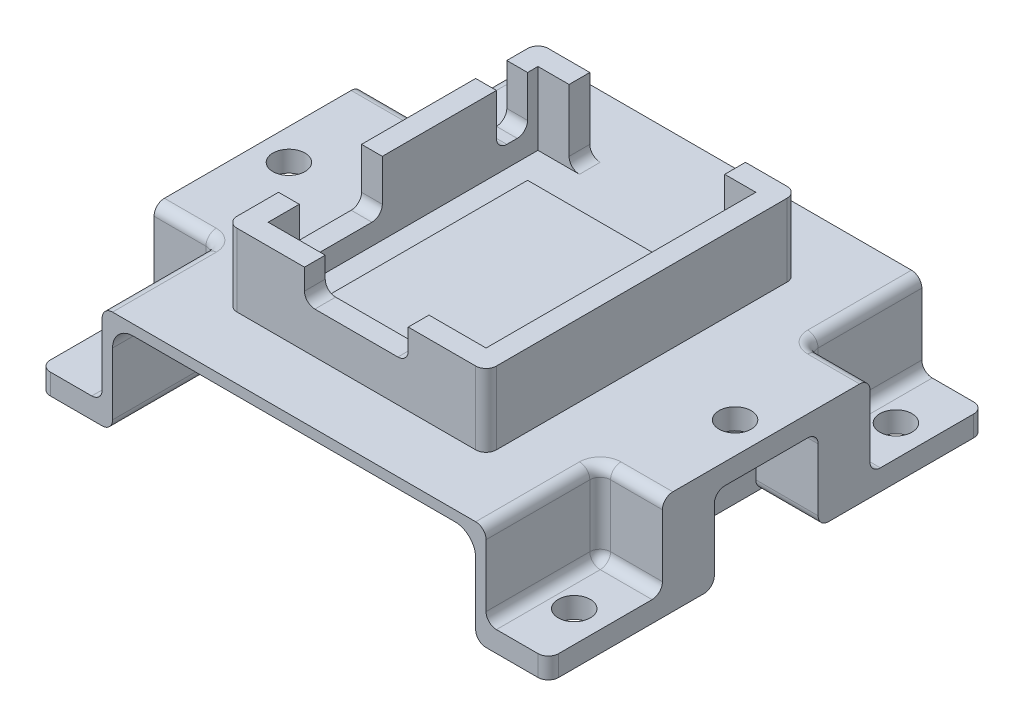
SolidWorks part; units mm, degrees
note: The reader was unsure of these and kept them because the rebuilt part matched: shared geometry of "Sketch1<3>", "Sketch4<4>", "Sketch7<3>", "Sketch9<3>", "Sketch9<4>", "Sketch9<5>".
material "PEI"
ref_plane "Front Plane" through (0, 0, 0) normal (0, 0, 1) x (1, 0, 0)
ref_plane "Top Plane" through (0, 0, 0) normal (0, 1, 0) x (1, 0, 0)
ref_plane "Right Plane" through (0, 0, 0) normal (1, 0, 0) x (0, 0, -1)
sketch "Sketch1" plane through (0, 0, 0) normal (0, 1, 0) x (1, 0, 0)
  line L0 (11.5, 14) -> (-11.5, 14)
  line L1 (10, -12.5) -> (-10, -12.5)
  line L2 (10, -12.5) -> (10, 12.5)
  line L3 (10, 12.5) -> (-10, 12.5)
  line L4 (-10, -12.5) -> (-10, 12.5)
  line L5 (10, -12.5) -> (-10, 12.5) construction
  line L6 (10, 12.5) -> (-10, -12.5) construction
  line L7 (-11.5, -14) -> (-11.5, 14)
  line L8 (11.5, -14) -> (-11.5, -14)
  line L9 (11.5, -14) -> (11.5, 14)
  point P0 (0, 0)
  dimension "D1" = 20
  dimension "D2" = 25
  dimension "D3" = 1.5
extrude "Boss-Extrude1" add sketch "Sketch1" along normal blind 5
extrude "Boss-Extrude2" add sketch "Sketch1<3>" along normal blind 1.5 contours L4 L1 L2 L3
sketch "Sketch1<3>" plane through (0, 0, 0) normal (0, 1, 0) x (1, 0, 0) same geometry as "Sketch1"
sketch "Sketch3" plane through (0, 0, 14) normal (0, 0, 1) x (1, 0, 0)
  line L0 (0, 0) -> (0, 5)
  line L1 (5, 0) -> (5, 5)
  line L2 (-5, 0) -> (-5, 5)
  line L3 (-5, 5) -> (5, 5)
  line L4 (-11.5, 0) -> (11.5, 0)
  line L5 (11.5, 0) -> (11.5, 5)
  line L6 (11.5, 5) -> (-11.5, 5)
  line L7 (-11.5, 5) -> (-11.5, 0)
  line L8 (-11.5, 0) -> (11.5, 0)
  line L9 (11.5, 0) -> (11.5, 5)
  line L10 (11.5, 5) -> (-11.5, 5)
  line L11 (-11.5, 5) -> (-11.5, 0)
  line L12 (-5, 1.5) -> (5, 1.5)
  line M10 (11.5, 5) -> (-11.5, 5)
  dimension "D4" = 3.5
  dimension "D1" = 0
  dimension "D2" = 5
  dimension "D3" = 5
extrude "Cut-Extrude1" cut sketch "Sketch3" against normal blind 5 contours L2 L12 L0 M10 | L0 L12 L1 M10
sketch "Sketch4" plane through (0, 0, 0) normal (0, -1, 0) x (1, 0, 0)
  line L0 (18.5, 21) -> (-18.5, 21)
  line L1 (17.5, -20) -> (-17.5, -20)
  line L2 (17.5, -20) -> (17.5, 20)
  line L3 (17.5, 20) -> (-17.5, 20)
  line L4 (11.5, -14) -> (11.5, 14)
  line L5 (11.5, 14) -> (-11.5, 14)
  line L6 (-11.5, 14) -> (-11.5, -14)
  line L7 (-11.5, -14) -> (11.5, -14)
  line L8 (11.5, -14) -> (11.5, 14)
  line L9 (11.5, 14) -> (-11.5, 14)
  line L10 (-11.5, 14) -> (-11.5, -14)
  line L11 (-11.5, -14) -> (11.5, -14)
  line L12 (-17.5, -20) -> (-17.5, 20)
  line L13 (17.5, -20) -> (-17.5, 20) construction
  line L14 (17.5, 20) -> (-17.5, -20) construction
  line L15 (-18.5, -21) -> (-18.5, 21)
  line L16 (18.5, -21) -> (-18.5, -21)
  line L17 (18.5, -21) -> (18.5, 21)
  line L18 (-17.5, 20) -> (-17.5, 21)
  line L19 (17.5, 20) -> (17.5, 21)
  line L20 (-17.5, -20) -> (-17.5, -21)
  line L21 (17.5, -20) -> (17.5, -21)
  point P2 (0, 0)
  line M7 (11.5, -14) -> (11.5, 14)
  line M8 (11.5, 14) -> (-11.5, 14)
  line M9 (-11.5, 14) -> (-11.5, -14)
  line M10 (-11.5, -14) -> (11.5, -14)
  dimension "D2" = 35
  dimension "D3" = 40
  dimension "D1" = 0
  dimension "D4" = 1
extrude "Boss-Extrude3" add sketch "Sketch4" along normal blind 10 contours L20 L12 L18 L0 L15 L16 | L2 L21 L16 L17 L0 L19
extrude "Boss-Extrude4" add sketch "Sketch4<4>" along normal blind 1 contours L3 L19 L0 L18 | L12 L1 L2 L3 M7 M10 M9 M8 | M10 M7 M8 M9 | L21 L1 L20 L16
sketch "Sketch4<4>" plane through (0, 0, 0) normal (0, -1, 0) x (1, 0, 0) same geometry as "Sketch4"
sketch "Sketch5" plane through (-18.5, 0, 0) normal (-1, 0, 0) x (0, 0, 1)
  line L1 (-21, -10) -> (21, -10)
  line L2 (-21, -10) -> (-21, -8)
  line L3 (-21, -8) -> (21, -8)
  line L4 (21, 0) -> (-21, 0)
  line L5 (-21, 0) -> (-21, -10)
  line L6 (-21, -10) -> (21, -10)
  line L7 (21, -10) -> (21, 0)
  line L8 (21, 0) -> (-21, 0)
  line L9 (-21, 0) -> (-21, -10)
  line L10 (-21, -10) -> (21, -10)
  line L11 (21, -10) -> (21, 0)
  line L12 (21, -10) -> (21, -8)
  line M8 (-21, 0) -> (-21, -10)
  line M9 (-21, -10) -> (21, -10)
  line M10 (21, -10) -> (21, 0)
  dimension "D2" = 2
  dimension "D1" = 0
extrude "Boss-Extrude5" add sketch "Sketch5" along normal blind 6 contours L3 M8 M9 M10
mirror "Mirror1" about plane through (0, 0, 0) normal (1, 0, 0) of "Boss-Extrude5"
sketch "Sketch6" plane through (0, 0, 21) normal (0, 0, 1) x (1, 0, 0)
  line L1 (-18.5, 0) -> (19.5, 0)
  line L2 (-18.5, 0) -> (-18.5, 30)
  line L3 (-18.5, 30) -> (19.5, 30)
  line L4 (19.5, 0) -> (19.5, 30)
  line L12 (18.5, 0) -> (-18.5, 0)
  line L13 (-18.5, 0) -> (-18.5, -8)
  line L14 (-18.5, -8) -> (-24.5, -8)
  line L15 (-24.5, -8) -> (-24.5, -10)
  line L16 (-24.5, -10) -> (-17.5, -10)
  line L17 (-17.5, -10) -> (-17.5, -1)
  line L18 (-17.5, -1) -> (17.5, -1)
  line L19 (17.5, -1) -> (17.5, -10)
  line L20 (17.5, -10) -> (24.5, -10)
  line L21 (24.5, -10) -> (24.5, -8)
  line L22 (24.5, -8) -> (18.5, -8)
  line L23 (18.5, -8) -> (18.5, 0)
  line L24 (18.5, 0) -> (-18.5, 0)
  line L25 (-18.5, 0) -> (-18.5, -8)
  line L26 (-18.5, -8) -> (-24.5, -8)
  line L27 (-24.5, -8) -> (-24.5, -10)
  line L28 (-24.5, -10) -> (-17.5, -10)
  line L29 (-17.5, -10) -> (-17.5, -1)
  line L30 (-17.5, -1) -> (17.5, -1)
  line L31 (17.5, -1) -> (17.5, -10)
  line L32 (17.5, -10) -> (24.5, -10)
  line L33 (24.5, -10) -> (24.5, -8)
  line L34 (24.5, -8) -> (18.5, -8)
  line L35 (18.5, -8) -> (18.5, 0)
  line M15 (18.5, 0) -> (-18.5, 0)
  dimension "D2" = 30
  dimension "D3" = 38
  dimension "D1" = 0
extrude "Cut-Extrude2" cut sketch "Sketch6" against normal through all contours L4 L3 L2 M15
sketch "Sketch7" plane through (0, 0, 0) normal (0, 1, 0) x (1, 0, 0)
  line L0 (0, 0) -> (24.5, 0)
  line L1 (24.5, -10) -> (-24.5, -10)
  line L2 (24.5, -10) -> (24.5, 10)
  line L3 (24.5, 10) -> (-24.5, 10)
  line L4 (18.5, 21) -> (-18.5, 21)
  line L5 (-18.5, 21) -> (-18.5, -21)
  line L6 (-18.5, -21) -> (18.5, -21)
  line L7 (18.5, -21) -> (18.5, 21)
  line L8 (18.5, 21) -> (-18.5, 21)
  line L9 (-18.5, 21) -> (-18.5, -21)
  line L10 (-18.5, -21) -> (18.5, -21)
  line L11 (18.5, -21) -> (18.5, 21)
  line L12 (-18.5, -21) -> (-18.5, 21)
  line L13 (-18.5, 21) -> (-24.5, 21)
  line L14 (-24.5, 21) -> (-24.5, -21)
  line L15 (-24.5, -21) -> (-18.5, -21)
  line L16 (-18.5, -21) -> (-18.5, 21)
  line L17 (-18.5, 21) -> (-24.5, 21)
  line L18 (-24.5, 21) -> (-24.5, -21)
  line L19 (-24.5, -21) -> (-18.5, -21)
  line L20 (18.5, 21) -> (18.5, -21)
  line L21 (18.5, -21) -> (24.5, -21)
  line L22 (24.5, -21) -> (24.5, 21)
  line L23 (24.5, 21) -> (18.5, 21)
  line L24 (18.5, 21) -> (18.5, -21)
  line L25 (18.5, -21) -> (24.5, -21)
  line L26 (24.5, -21) -> (24.5, 21)
  line L27 (24.5, 21) -> (18.5, 21)
  line L28 (-24.5, -10) -> (-24.5, 10)
  line L29 (24.5, -10) -> (-24.5, 10) construction
  line L30 (24.5, 10) -> (-24.5, -10) construction
  line L31 (24.5, 0) -> (-29.6061, 0)
  line L32 (18.5, 10) -> (24.5, -10)
  line L33 (-24.5, -10) -> (-18.5, 10)
  line L34 (0, 0) -> (0, -21) construction
  circle A0 centre (21.5, 0) radius 1.55
  circle A1 centre (-21.5, 0) radius 1.55
  point P4 (0, 0)
  point P25 (21.5, 0)
  line M16 (-18.5, 21) -> (-18.5, -21)
  line M18 (18.5, -21) -> (18.5, 21)
  dimension "D5" = 3.1
  dimension "D4" = 20
  dimension "D1" = 0
  dimension "D2" = 0
  dimension "D3" = 0
extrude "Cut-Extrude3" cut sketch "Sketch7" against normal blind 10 contours A0 L0 L2 L3 L32 | A0 L32 L2 L0 | A0 L32 L0 M18 | L32 A0 L31 | L31 A0 L32 | L31 A0 L32 | L32 A0 L31 | A1 L33 L31 | A1 L31 L33 | A1 L31 L33 | A1 L33 L31 | L33 A1 L31 M16 | L31 A1 L33 L1 L16 | L33 A1 L31 L28 | A0 L0 L1 L32 M18 | L31 A1 L33 L3 L18
extrude "Boss-Extrude6" add sketch "Sketch7<3>" against normal blind 2 contours L3 L18 L1 M16 | L2 L3 L1 M18 | A0 L32 L2 L0 | A0 L0 L2 L3 L32 | A0 L32 L0 M18 | L31 A1 L33 L1 L16 | L33 A1 L31 L28 | L33 A1 L31 M16
sketch "Sketch7<3>" plane through (0, 0, 0) normal (0, 1, 0) x (1, 0, 0) same geometry as "Sketch7"
sketch "Sketch8" plane through (0, -10, 0) normal (0, -1, 0) x (1, 0, 0)
  line L0 (18.5, -10) -> (18.5, -21)
  line L1 (24.5, 10) -> (18.5, 21)
  line L2 (18.5, -10) -> (24.5, -21)
  line L3 (18.5, 10) -> (18.5, 21)
  line L4 (18.5, 10) -> (24.5, 21)
  line L5 (18.5, -21) -> (24.5, -10)
  line L8 (18.5, -10) -> (18.5, 10)
  line L9 (18.5, 10) -> (24.5, 10)
  line L10 (24.5, 10) -> (24.5, 21)
  line L11 (24.5, 21) -> (17.5, 21)
  line L12 (17.5, 21) -> (17.5, -21)
  line L13 (17.5, -21) -> (24.5, -21)
  line L14 (24.5, -21) -> (24.5, -10)
  line L15 (24.5, -10) -> (18.5, -10)
  line L16 (18.5, -10) -> (18.5, 10)
  line L17 (18.5, 10) -> (24.5, 10)
  line L18 (24.5, 10) -> (24.5, 21)
  line L19 (24.5, 21) -> (17.5, 21)
  line L20 (17.5, 21) -> (17.5, -21)
  line L21 (17.5, -21) -> (24.5, -21)
  line L22 (24.5, -21) -> (24.5, -10)
  line L23 (24.5, -10) -> (18.5, -10)
  circle A0 centre (21.5, -15.5) radius 1.55
  circle A1 centre (21.5, 15.5) radius 1.55
  dimension "D2" = 3.1
  dimension "D3" = 3.1
  dimension "D1" = 0
extrude "Cut-Extrude4" cut sketch "Sketch8" against normal blind 2 contours L1 A1 L4 | L4 A1 L1 | L4 A1 L1 | L1 A1 L4 | L2 A0 L5 | L5 A0 L2 | L2 A0 L5 | L5 A0 L2
mirror "Mirror2" about plane through (0, 0, 0) normal (1, 0, 0) of "Cut-Extrude4"
sketch "Sketch9" plane through (0, 0, 0) normal (0, 1, 0) x (1, 0, 0)
  line L0 (-12.5, -15) -> (-12.5, 15)
  line L1 (-18.5, 21) -> (18.5, 21)
  line L2 (-18.5, 21) -> (-18.5, -21)
  line L3 (-18.5, -21) -> (18.5, -21)
  line L4 (18.5, 21) -> (18.5, -21)
  line L5 (10.5, -13) -> (-10.5, -13)
  line L6 (10.5, -13) -> (10.5, 13)
  line L7 (10.5, 13) -> (-10.5, 13)
  line L8 (-10.5, -13) -> (-10.5, 13)
  line L9 (10.5, -13) -> (-10.5, 13) construction
  line L10 (10.5, 13) -> (-10.5, -13) construction
  line L11 (12.5, 15) -> (-12.5, 15)
  line L12 (18.5, 21) -> (-18.5, 21)
  line L13 (-18.5, 21) -> (-18.5, 10)
  line L14 (-18.5, 10) -> (-24.5, 10)
  line L15 (-24.5, 10) -> (-24.5, -10)
  line L16 (-24.5, -10) -> (-18.5, -10)
  line L17 (-18.5, -10) -> (-18.5, -21)
  line L18 (-18.5, -21) -> (18.5, -21)
  line L19 (18.5, -21) -> (18.5, -10)
  line L20 (18.5, -10) -> (24.5, -10)
  line L21 (24.5, -10) -> (24.5, 10)
  line L22 (24.5, 10) -> (18.5, 10)
  line L23 (18.5, 10) -> (18.5, 21)
  line L24 (18.5, 21) -> (-18.5, 21)
  line L25 (-18.5, 21) -> (-18.5, 10)
  line L26 (-18.5, 10) -> (-24.5, 10)
  line L27 (-24.5, 10) -> (-24.5, -10)
  line L28 (-24.5, -10) -> (-18.5, -10)
  line L29 (-18.5, -10) -> (-18.5, -21)
  line L30 (-18.5, -21) -> (18.5, -21)
  line L31 (18.5, -21) -> (18.5, -10)
  line L32 (18.5, -10) -> (24.5, -10)
  line L33 (24.5, -10) -> (24.5, 10)
  line L34 (24.5, 10) -> (18.5, 10)
  line L35 (18.5, 10) -> (18.5, 21)
  line L36 (12.5, -15) -> (12.5, 15)
  line L37 (12.5, -15) -> (-12.5, -15)
  line L38 (-10.5, 13) -> (-10.5, 12)
  line L39 (5, -17) -> (-5, -17)
  line L40 (5, -17) -> (5, -13)
  line L41 (5, -13) -> (-5, -13)
  line L42 (-5, -17) -> (-5, -13)
  line L43 (5, -17) -> (-5, -13) construction
  line L44 (5, -13) -> (-5, -17) construction
  line L45 (-10.5, 12) -> (-12.5, 12)
  line L46 (-12.5, 12) -> (-12.5, -10)
  line L47 (-12.5, -10) -> (-10.5, -10)
  line L48 (-10.5, -10) -> (-10.5, -13)
  line L49 (10.5, -13) -> (10.5, 13)
  line L50 (7.5, 13) -> (7.5, 15)
  line L51 (7.5, 15) -> (-7.5, 15)
  line L52 (-7.5, 15) -> (-7.5, 13)
  line L53 (-12.5, 9) -> (-10.5, 9)
  line L54 (-12.5, -2) -> (-10.5, -2)
  line L55 (-5.5, -13) -> (-5.5, 7)
  line L56 (-5.5, 7) -> (10.5, 7)
  point P2 (0, 0)
  point P20 (0, -15)
  point P33 (-7.5, 14)
  dimension "D2" = 21
  dimension "D3" = 26
  dimension "D5" = 10
  dimension "D6" = 3
  dimension "D7" = 1
  dimension "D8" = 3
  dimension "D9" = 3
  dimension "D10" = 3
  dimension "D11" = 8
  dimension "D12" = 16
  dimension "D13" = 20
  dimension "D1" = 0
  dimension "D4" = 2
extrude "Boss-Extrude7" add sketch "Sketch9" along normal blind 7 contours L52 L11 L0 L45 L8 L7 | L46 L54 L8 L53 | L47 L0 L37 L42 L5 L8 | L50 L7 L49 L6 L5 L40 L37 L36 L11
extrude "Boss-Extrude8" add sketch "Sketch9<3>" along normal blind 3 contours L56 L55 L5 L6
sketch "Sketch9<3>" plane through (0, 0, 0) normal (0, 1, 0) x (1, 0, 0) same geometry as "Sketch9"
extrude "Boss-Extrude9" add sketch "Sketch9<4>" along normal blind 2 contours L46 L53 L8 L45 | L54 L0 L47 L8
sketch "Sketch9<4>" plane through (0, 0, 0) normal (0, 1, 0) x (1, 0, 0) same geometry as "Sketch9"
extrude "Boss-Extrude10" add sketch "Sketch9<5>" along normal blind 4 contours L42 L37 L40 L5
sketch "Sketch9<5>" plane through (0, 0, 0) normal (0, 1, 0) x (1, 0, 0) same geometry as "Sketch9"
sketch "Sketch10" plane through (0, 0, -10) normal (0, 0, 1) x (1, 0, 0)
  line L0 (-18.5, -8) -> (-18.5, -2)
  line L1 (-18.5, -2) -> (-24.5, -2)
  line L2 (-18.5, -2) -> (-24.5, -2) construction
  line L3 (-24.5, -2) -> (-24.5, -8)
  line L4 (-18.5, -8) -> (-24.5, -8)
  line L5 (-24.5, -8) -> (-24.5, -10)
  line L6 (-24.5, -10) -> (-18.5, -10)
  line L7 (-18.5, -10) -> (-18.5, -8)
  line L8 (-18.5, -8) -> (-24.5, -8)
  line L9 (-24.5, -8) -> (-24.5, -10)
  line L10 (-24.5, -10) -> (-18.5, -10)
  line L11 (-18.5, -10) -> (-18.5, -8)
  line M5 (-18.5, -8) -> (-24.5, -8)
  line M6 (-24.5, -8) -> (-24.5, -10)
  line M7 (-24.5, -10) -> (-18.5, -10)
  line M8 (-18.5, -10) -> (-18.5, -8)
  dimension "D1" = 0
extrude "Boss-Extrude11" add sketch "Sketch10" along normal blind 5 contours M8 M5 M6 M7 | L1 L3 L0 M5
fillet "Fillet1" radius 1 3 edges at (-18.5, -8, -15.5) (-21.5, -8, -10) (-18.5, -4, -10)
fillet "Fillet2" radius 2 2 edges at (17.5, -1, 0) (-17.5, -1, 0)
fillet "Fillet3" radius 1 2 edges at (17.5, -10, 0) (-17.5, -10, 0)
mirror "Mirror3" about plane through (0, 0, 0) normal (0, 0, 1) of "Boss-Extrude11"
mirror "Mirror4" about plane through (0, 0, 0) normal (1, 0, 0) of "Mirror3", "Boss-Extrude11"
fillet "Fillet4" radius 1 18 edges at (-21.5, 0, 10) (-21.5, -8, 10) (21.5, 0, -10) (21.5, -8, -10) (18.5, -8, 15.5) (18.5, 0, 15.5) (-18.5, 0, -16) (-18.7929, 0, -10.2929) (-22, 0, -10) (-18.5, -8, 15.5) (-18.5, 0, 15.5) (18.5, -8, -15.5) (18.5, 0, -15.5) (21.5, 0, 10) (21.5, -8, 10) (18.5, -4, -10) (18.5, -4, 10) (-18.5, -4, 10)
fillet "Fillet5" radius 1 12 edges at (-24.5, -9, -21) (-24.5, -9, 21) (24.5, -9, 21) (24.5, -9, -21) (-21.5, -2, -5) (-21.5, -10, -5) (-21.5, -10, 5) (-21.5, -2, 5) (21.5, -2, 5) (21.5, -10, 5) (21.5, -10, -5) (21.5, -2, -5)
fillet "Fillet6" radius 1 12 edges at (7.5, 0, -14) (-7.5, 0, -14) (-11.5, 2, -12) (-11.5, 2, -9) (-11.5, 2, 10) (-11.5, 2, 2) (-5, 4, 14) (5, 4, 14) (12.5, 3.5, 15) (-12.5, 3.5, 15) (-12.5, 3.5, -15) (12.5, 3.5, -15)
